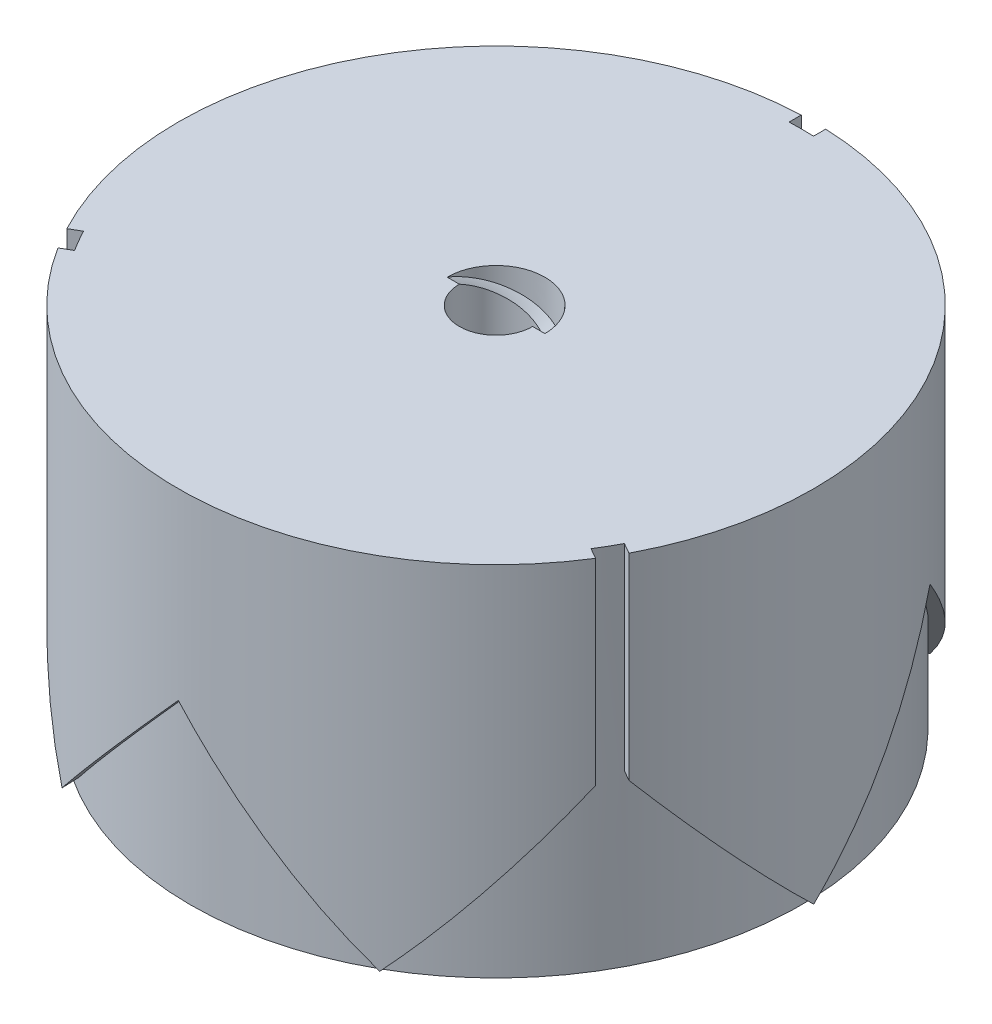
SolidWorks part; units mm, degrees
ref_plane "Front Plane" through (0, 0, 0) normal (0, 0, 1) x (1, 0, 0)
ref_plane "Top Plane" through (0, 0, 0) normal (0, 1, 0) x (1, 0, 0)
ref_plane "Right Plane" through (0, 0, 0) normal (1, 0, 0) x (0, 0, -1)
sketch "Sketch1" plane through (0, 0, 0) normal (0, 1, 0) x (1, 0, 0)
  circle A0 centre (0, 0) radius 13
  dimension "D1" = 26
extrude "Boss-Extrude1" add sketch "Sketch1" along normal blind 15
sketch "Sketch5" plane through (0, 15, 0) normal (0, 1, 0) x (1, 0, 0)
  line L0 (0, 0) -> (0, 17.3252) construction
  line L1 (-0.5, 16.6552) -> (0.5, 16.6552)
  line L2 (-0.5, 16.6552) -> (-0.5, 12.49)
  line L4 (0.5, 16.6552) -> (0.5, 12.49)
  arc A0 (0.5, 12.49) -> (-0.5, 12.49) centre (0, 0) ccw
  dimension "D1" = 25
  dimension "D2" = 0.5
extrude "Cut-Extrude2" cut sketch "Sketch5" against normal blind 15
pattern_circular "CirPattern1" count 3 over 360 about axis through (0, 15, 0) along (0, 1, 0) of "Cut-Extrude2"
ref_plane "Plane1" through (0, 0, -20) normal (0, 0, 1) x (1, 0, 0)
sketch "Sketch6" plane through (0, 0, -20) normal (0, 0, 1) x (1, 0, 0)
  line L0 (0, 0) -> (0, 14.6337) construction
  line L2 (0, 7.5) -> (-6.75, 0)
  line L4 (-13, 0) -> (-0.5, 0) construction
  line L5 (-6.75, 0) -> (6.75, 0)
  line L7 (0.5, 0) -> (13, 0) construction
  line L8 (6.75, 0) -> (0, 7.5)
  dimension "D1" = 7.5
extrude "Cut-Extrude3" cut sketch "Sketch6" against normal through all both and the other way through all
pattern_circular "CirPattern2" count 3 over 360 about axis through (0, 15, 0) along (0, 1, 0) of "Cut-Extrude3"
sketch "Sketch7" plane through (0, 0, 0) normal (0, 1, 0) x (1, 0, 0)
  circle A0 centre (0, 0) radius 12.5
  dimension "D1" = 25
extrude "Boss-Extrude2" add sketch "Sketch7" along normal blind 10
sketch "Sketch2" plane through (0, 15, 0) normal (0, 1, 0) x (1, 0, 0)
  circle A0 centre (0, 0) radius 1.5
  dimension "D1" = 3
extrude "Cut-Extrude1" cut sketch "Sketch2" against normal blind 15
sketch "Sketch3" plane through (0, 15, 0) normal (0, 1, 0) x (1, 0, 0)
  circle A1 centre (0, 0) radius 2
  dimension "D1" = 4
curve "Helix/Spiral1" pitch 5 height 15 radius 2 centre (0, 15, 0) axis (0, -1, 0) start towards (0, 0, 1)
sketch "Sketch4" plane through (0, 0, 0) normal (0, 0, 1) x (1, 0, 0)
  line L1 (-2, 15) -> (-1.5, 15)
  line L2 (-2, 15) -> (-2, 17.5)
  line L3 (-2, 17.5) -> (-1.5, 17.5)
  line L4 (-1.5, 15) -> (-1.5, 17.5)
  dimension "D1" = 2.5
  dimension "D2" = 0.5
  dimension "D3" = 1.5
sweep "Cut-Sweep2" cut profiles "Sketch4" path "Helix/Spiral1" align with end faces yes
scale "Scale1" scale about origin uniform scaling yes scale factor 0.655
